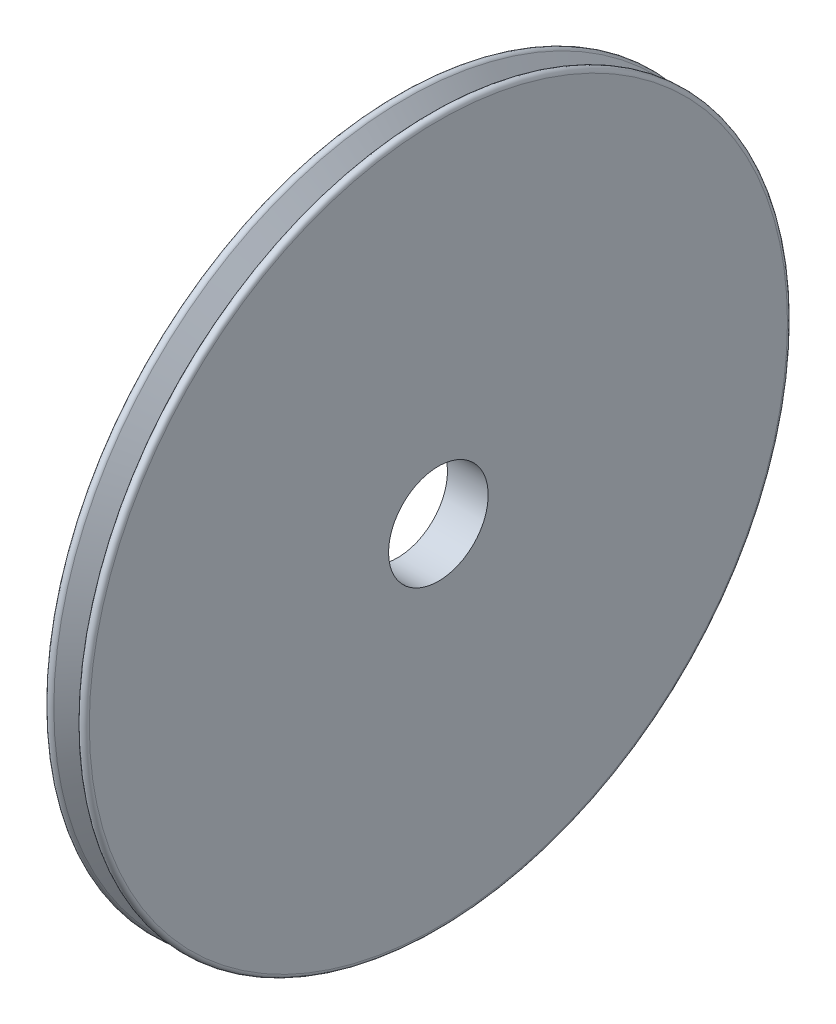
SolidWorks part; units mm, degrees
ref_plane "Front Plane" through (0, 0, 0) normal (0, 0, 1) x (1, 0, 0)
ref_plane "Top Plane" through (0, 0, 0) normal (0, 1, 0) x (1, 0, 0)
ref_plane "Right Plane" through (0, 0, 0) normal (1, 0, 0) x (0, 0, -1)
sketch "Sketch1" plane through (0, 0, 0) normal (0, 0, 1) x (1, 0, 0)
  line L0 (0, 0) -> (0, 63.1756) construction
  line L1 (-3.57, 0) -> (3.57, 0)
  line L2 (3.57, 0) -> (3.57, 63.5)
  line L3 (3.57, 63.5) -> (0, 58.5)
  line L4 (0, 58.5) -> (0, 0)
  line L5 (-3.57, 63.5) -> (0, 58.5)
  line L6 (-3.57, 0) -> (-3.57, 63.5)
  line L7 (0, 0) -> (65.8087, 0) construction
  dimension "D1" = 3.57
  dimension "D2" = 63.5
  dimension "D3" = 58.5
revolve "Revolve1" add sketch "Sketch1" angle 360 about L7 region at (-1.8094, 30.5171, 0) region at (1.8094, 30.5171, 0)
fillet "Fillet1" radius 0.75 2 edges at (-3.57, 0, 63.5) (3.57, 0, 63.5)
sketch "Sketch2" plane through (0, 0, 0) normal (1, 0, 0) x (0, 0, -1)
  circle A0 centre (0, 0) radius 8.73
  dimension "D1" = 17.46
extrude "Cut-Extrude1" cut sketch "Sketch2" against normal mid plane 10
